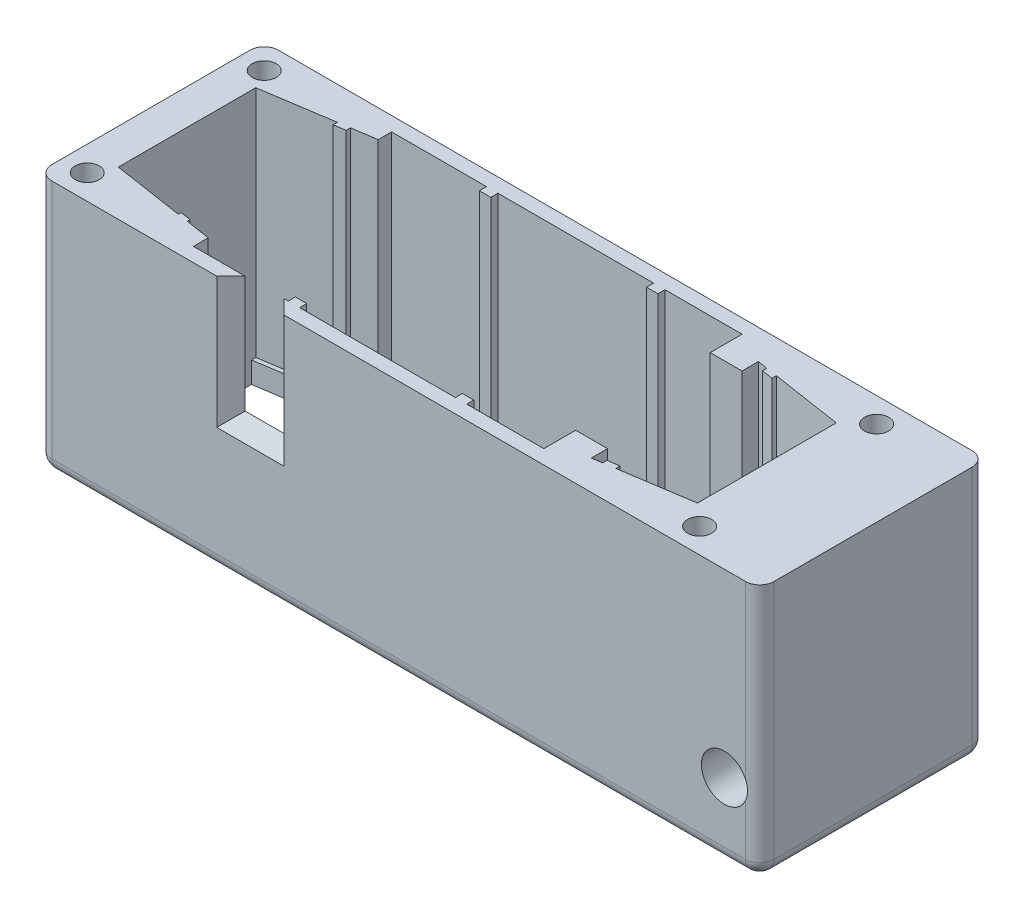
SolidWorks part; units mm, degrees
ref_plane "Front Plane" through (0, 0, 0) normal (0, 0, 1) x (1, 0, 0)
ref_plane "Top Plane" through (0, 0, 0) normal (0, 1, 0) x (1, 0, 0)
ref_plane "Right Plane" through (0, 0, 0) normal (1, 0, 0) x (0, 0, -1)
sketch "Sketch1" plane through (0, 0, 0) normal (0, 1, 0) x (1, 0, 0)
  line L0 (-28.64, -4.3272) -> (-28.64, -2.8272)
  line L1 (-28.64, 21.6728) -> (23.36, 21.6728)
  line L2 (-43.64, 17.8728) -> (-43.64, -0.5272)
  line L3 (-28.64, -4.3272) -> (23.36, -4.3272)
  line L4 (38.36, 17.8728) -> (38.36, -0.5272)
  line L5 (-28.64, -2.8272) -> (-43.64, -0.5272)
  line L6 (-43.64, 8.6728) -> (43.06, 8.6728) construction
  line L7 (-2.64, 26.6728) -> (-2.64, -4.3272) construction
  line L8 (23.36, -2.8272) -> (38.36, -0.5272)
  line L9 (23.36, -4.3272) -> (23.36, -2.8272)
  line L10 (-28.64, 21.6728) -> (-28.64, 20.1728)
  line L11 (-28.64, 20.1728) -> (-43.64, 17.8728)
  line L12 (23.36, 20.1728) -> (38.36, 17.8728)
  line L13 (23.36, 21.6728) -> (23.36, 20.1728)
  line L15 (-48.64, 24.6728) -> (53.36, 24.6728)
  line L16 (-48.64, 24.6728) -> (-48.64, -7.3272)
  line L17 (-48.64, -7.3272) -> (53.36, -7.3272)
  line L18 (53.36, 24.6728) -> (53.36, -7.3272)
  dimension "D1" = 82
  dimension "D2" = 15
  dimension "D3" = 1.5
  dimension "D4" = 9.2
  dimension "D5" = 15
  dimension "D6" = 5
  dimension "D7" = 3
  dimension "D8" = 3
  dimension "D9" = 26
extrude "main-body" add sketch "Sketch1" along normal blind 36
sketch "Sketch3" plane through (0, 36, 0) normal (0, 1, 0) x (1, 0, 0)
  line L0 (9.96, 22.6728) -> (23.36, 22.6728)
  line L1 (26.76, -2.3058) -> (28.36, -2.0605)
  line L2 (28.36, -2.6675) -> (38.36, -1.1342)
  line L3 (-2.64, 28.1728) -> (-2.64, -10.6272) construction
  line L6 (-33.64, 20.0132) -> (-33.64, 19.4062)
  line L7 (-28.64, 21.6728) -> (-28.6365, 20.7804)
  line L8 (-43.64, 18.4798) -> (-43.64, -0.9342)
  line L9 (-28.6365, -3.2347) -> (-32.14, -2.6975)
  line L10 (-13.64, -5.3272) -> (8.36, -5.3272)
  line L11 (-33.64, 20.0132) -> (-43.64, 18.4798)
  line L12 (-32.04, 19.6515) -> (-32.04, 20.2585)
  line L13 (-28.64, 20.1728) -> (-43.64, 17.8728) construction
  line L14 (-32.04, 19.6515) -> (-33.64, 19.4062)
  line L15 (-43.64, 17.8728) -> (-43.64, -0.5272) construction
  line L16 (-13.64, -5.3272) -> (-13.64, -4.3272)
  line L17 (23.36, 21.6728) -> (-28.64, 21.6728) construction
  line L18 (-28.64, 21.6728) -> (-28.64, 22.6728)
  line L19 (-28.64, 22.6728) -> (-15.24, 22.6728)
  line L20 (-15.24, -4.3272) -> (-13.64, -4.3272)
  line L21 (-15.24, -5.3272) -> (-15.24, -4.3272)
  line L22 (-15.24, 22.6728) -> (-15.24, 21.6728)
  line L23 (-15.24, 21.6728) -> (-13.64, 21.6728)
  line L24 (-13.64, 22.6728) -> (-13.64, 21.6728)
  line L25 (-13.64, 22.6728) -> (8.36, 22.6728)
  line L26 (-28.64, -5.3272) -> (-15.24, -5.3272)
  line L27 (-28.64, -4.1272) -> (-28.64, -5.3272)
  line L28 (-32.14, -2.0905) -> (-33.64, -1.8605)
  line L29 (-32.14, -2.0905) -> (-32.14, -2.6975)
  line L30 (-33.64, -2.4675) -> (-43.64, -0.9342)
  line L31 (-28.64, -4.1272) -> (-28.6365, -3.2347)
  line L32 (-33.64, -2.4675) -> (-33.64, -1.8605)
  line L33 (23.36, 22.6728) -> (23.36, 20.7798)
  line L34 (23.36, 20.1728) -> (23.36, 21.6728) construction
  line L35 (23.36, 20.7798) -> (26.76, 20.2585)
  line L36 (38.36, 17.8728) -> (23.36, 20.1728) construction
  line L37 (38.36, -0.5272) -> (38.36, 17.8728) construction
  line L38 (38.36, -1.1342) -> (38.36, 18.4798)
  line L39 (9.96, -5.3272) -> (23.36, -5.3272)
  line L40 (23.36, -5.3272) -> (23.36, -3.4342)
  line L41 (8.36, 22.6728) -> (8.36, 21.6728)
  line L42 (9.96, 21.6728) -> (8.36, 21.6728)
  line L43 (9.96, 22.6728) -> (9.96, 21.6728)
  line L44 (9.96, -5.3272) -> (9.96, -4.3272)
  line L45 (9.96, -4.3272) -> (8.36, -4.3272)
  line L46 (23.36, -4.3272) -> (23.36, -2.8272) construction
  line L47 (23.36, -3.4342) -> (26.76, -2.9129)
  line L48 (8.36, -5.3272) -> (8.36, -4.3272)
  line L49 (23.36, -2.8272) -> (38.36, -0.5272) construction
  line L50 (-28.64, -4.3272) -> (23.36, -4.3272) construction
  line L51 (28.36, 20.0132) -> (28.36, 19.4062)
  line L52 (26.76, -2.9129) -> (26.76, -2.3058)
  line L53 (26.76, 19.6515) -> (26.76, 20.2585)
  line L54 (28.36, 20.0132) -> (38.36, 18.4798)
  line L55 (26.76, 19.6515) -> (28.36, 19.4062)
  line L56 (-28.7309, 20.7659) -> (-43.7309, 18.4659)
  line L57 (-28.6365, 20.7804) -> (-32.04, 20.2585)
  line L58 (-43.64, 8.7728) -> (38.36, 8.7728) construction
  line L59 (28.36, -2.0605) -> (28.36, -2.6675)
  point P15 (-2.64, 30.1728)
  point P45 (-43.64, 8.7728)
  point P57 (-2.64, 22.6728)
  point P65 (-43.64, 8.7728)
  point P74 (-2.64, -5.3272)
  dimension "D1" = 1.6
  dimension "D2" = 10
  dimension "D3" = 1.6
  dimension "D4" = 1
  dimension "D5" = 11
  dimension "D7" = 0.6
  dimension "D8" = 0.6
  dimension "D9" = 1
  dimension "D10" = 10
  dimension "D11" = 1.6
  dimension "D12" = 41
  dimension "D6" = 0.6
extrude "clip-clearance" cut sketch "Sketch3" against normal offset from surface (33 mm away) 3 up to face at (2.36, 0, -8.6728)
sketch "Sketch4" plane through (0, 0, 0) normal (0, 1, 0) x (1, 0, 0)
  line L1 (23.36, 22.6728) -> (9.96, 22.6728) construction
  line L2 (20.8573, 22.6728) -> (25.3573, 22.6728)
  line L3 (20.8573, 22.6728) -> (20.8573, 18.1728)
  line L4 (20.8573, 18.1728) -> (25.3573, 18.1728)
  line L6 (-48.64, 8.6728) -> (53.36, 8.6728) construction
  line L8 (25.3573, 22.6728) -> (25.3573, 18.1728)
  line L9 (9.96, -5.3272) -> (23.36, -5.3272) construction
  line L10 (20.8573, -5.3272) -> (25.3573, -5.3272)
  line L11 (20.8573, -5.3272) -> (20.8573, -0.8272)
  line L17 (20.8573, -0.8272) -> (25.3573, -0.8272)
  line L18 (25.3573, -5.3272) -> (25.3573, -0.8272)
  line L19 (38.36, -1.1342) -> (38.36, 18.4798) construction
  line L20 (-48.64, 24.6728) -> (-48.64, -7.3272) construction
  line L21 (53.36, -7.3272) -> (53.36, 24.6728) construction
  dimension "D1" = 13.0028
  dimension "D2" = 13.0028
  dimension "D3" = 4.5
  dimension "D4" = 9.5
  dimension "D5" = 9.5
extrude "clip-guide" add sketch "Sketch4" along normal up to surface (36 mm away) up to face at (-2.6445, 36, -8.6917)
sketch "Sketch22" plane through (0, 0, 7.3272) normal (0, 0, 1) x (1, 0, 0)
  line L0 (-48.64, 36) -> (53.36, 36) construction
  line L1 (-16.34, 36) -> (-20.84, 36)
  line L2 (-16.34, 36) -> (-16.34, 20)
  line L3 (-16.34, 20) -> (-20.84, 20)
  line L4 (-20.84, 36) -> (-20.84, 20)
  line L5 (-48.64, 36) -> (-48.64, 0) construction
  line L7 (-48.64, 0) -> (53.36, 0) construction
  dimension "D1" = 27.8
  dimension "D2" = 4.5
  dimension "D3" = 20
extrude "clip-window" cut sketch "Sketch22" against normal up to next
sketch "Sketch5" plane through (53.36, 0, 0) normal (1, 0, 0) x (0, 0, -1)
  line L1 (2.6728, 22.82) -> (14.6728, 22.82)
  line L2 (2.6728, 22.82) -> (2.6728, 16.82)
  line L3 (2.6728, 16.82) -> (14.6728, 16.82)
  line L4 (14.6728, 22.82) -> (14.6728, 16.82)
  line L5 (-7.3272, 0) -> (24.6728, 0) construction
  line L6 (-7.3272, 36) -> (24.6728, 36) construction
  line L7 (8.6728, 36) -> (8.6728, 0) construction
  dimension "D1" = 22.82
  dimension "D2" = 6
  dimension "D3" = 12
  dimension "D4" = 6
extrude "lock_clearance" cut sketch "Sketch5" against normal offset from surface (18.5 mm away) 3.5 up to face at (38.36, 10.5, -8.6728) offset beyond the face yes
sketch "Sketch7" plane through (53.36, 0, 0) normal (1, 0, 0) x (0, 0, -1)
  line L0 (-7.3272, 0) -> (24.6728, 0) construction
  line L1 (2.6728, 16.82) -> (14.6728, 16.82)
  line L2 (2.6728, 16.82) -> (2.6728, 0)
  line L3 (2.6728, 0) -> (14.6728, 0)
  line L4 (14.6728, 16.82) -> (14.6728, 0)
  line L5 (14.6728, 16.82) -> (14.6728, 22.82) construction
extrude "lock_mech_clearance" cut sketch "Sketch7" against normal blind 10
sketch "Sketch26" plane through (0, 0, -14.6728) normal (0, 0, 1) x (1, 0, 0)
  line L0 (53.36, 22.82) -> (53.36, 0)
  line L1 (52.16, 2.5004) -> (50.86, 1.2004)
  line L2 (43.36, 0) -> (53.36, 0) construction
  line L3 (52.16, 2.5004) -> (52.16, 22.82)
  line L4 (38.36, 22.82) -> (53.36, 22.82) construction
  line L5 (53.36, 22.82) -> (52.16, 22.82)
  line L6 (53.36, 0) -> (50.86, 0)
  line L9 (50.86, 0) -> (50.86, 1.2004)
  dimension "D1" = 2.5
  dimension "D2" = 45
  dimension "D3" = 1.2
  dimension "D4" = 1.2004
extrude "lock_mech_cover" add sketch "Sketch26" along normal up to surface (12 mm away) up to face at (45.0267, 13.2133, -2.6728)
sketch "Sketch28" plane through (38.36, 0, 0) normal (-1, 0, 0) x (0, 0, 1)
  line L0 (-2.6728, 22.82) -> (-14.6728, 22.82) construction
  line L1 (-14.6728, 22.82) -> (-15.6728, 22.82)
  line L2 (-14.6728, 22.82) -> (-14.6728, 16.82)
  line L3 (-14.6728, 16.82) -> (-15.6728, 16.82)
  line L4 (-15.6728, 22.82) -> (-15.6728, 16.82)
  line L5 (-2.6728, 16.82) -> (-1.6728, 16.82)
  line L6 (-2.6728, 16.82) -> (-2.6728, 22.82)
  line L7 (-2.6728, 22.82) -> (-1.6728, 22.82)
  line L8 (-1.6728, 16.82) -> (-1.6728, 22.82)
  line L10 (-14.6728, 22.82) -> (-14.6728, 16.82) construction
  dimension "D1" = 1
  dimension "D2" = 1
extrude "lock_slide_clearance" cut sketch "Sketch28" against normal up to surface (13.8 mm away) up to face at (52.16, 12.6602, -8.6728)
sketch "Sketch27" plane through (0, 0, -14.6728) normal (0, 0, 1) x (1, 0, 0)
  line L0 (43.36, 0) -> (43.36, 4.5)
  line L1 (43.36, 0) -> (43.36, 16.82) construction
  line L2 (43.36, 4.5) -> (41.6257, 0)
  line L3 (53.36, 0) -> (-48.64, 0) construction
  line L4 (41.6257, 0) -> (43.36, 0)
  dimension "D1" = 4.5
  dimension "D2" = 1.7343
extrude "lock lever space" cut sketch "Sketch27" along normal up to surface (12 mm away) up to face at (48.7934, 6.2235, -2.6728)
hole_wizard "CBORE for M3 Hex Socket Thin Head Cap Screw2" positions "Sketch24" profile "Sketch23" counterbore size "M3" standard "DIN"
sketch "Sketch24" plane through (0, 0, 7.3272) normal (0, 0, 1) x (1, 0, 0)
  line L0 (53.36, 36) -> (53.36, 0) construction
  line L1 (-16.34, 36) -> (53.36, 36) construction
  point P0 (48.36, 10.5)
  dimension "D1" = 5
  dimension "D2" = 25.5
sketch "Sketch23" plane through (48.36, 10.5, 7.3272) normal (1, 0, 0) x (0, -1, 0)
  line L0 (0, 0) -> (0, 11.9614)
  line L1 (0, 11.9614) -> (1.6, 11)
  line L2 (1.6, 11) -> (1.6, 7.4)
  line L3 (1.6, 7.4) -> (3.25, 7.4)
  line L4 (3.25, 7.4) -> (3.25, 0)
  line L5 (3.25, 0) -> (0, 0)
  line L10 (0, 11.9614) -> (-1.6, 11) construction
  line L11 (0, -6.35) -> (0, 107.95) construction
  dimension "Hole Dia." = 3.2
  dimension "Hole Depth" = 11
  dimension "C'Bore Dia." = 6.5
  dimension "C'Bore Depth" = 7.4
  dimension "Drill Angle" = 118
hole_wizard "CBORE for M3 Hex Socket Thin Head Cap Screw1" positions "Sketch9" profile "Sketch8" counterbore size "M3" standard "DIN" end condition through all
sketch "Sketch9" plane through (0, 0, 0) normal (0, -1, 0) x (-1, 0, 0)
  line L0 (-53.36, -7.3272) -> (-53.36, 24.6728) construction
  line L1 (-53.36, 24.6728) -> (48.64, 24.6728) construction
  line L2 (48.64, -7.3272) -> (-53.36, -7.3272) construction
  line L3 (48.64, 24.6728) -> (48.64, -7.3272) construction
  point P0 (45.14, -3.8272)
  point P2 (-41.36, -3.8272)
  point P4 (-41.36, 21.1728)
  point P6 (45.14, 21.1728)
  dimension "D1" = 12
  dimension "D2" = 3.5
  dimension "D3" = 3.5
  dimension "D4" = 3.5
sketch "Sketch8" plane through (-45.14, 0, 3.8272) normal (1, 0, 0) x (0, 0, -1)
  line L0 (0, 0) -> (0, 36)
  line L1 (0, 36) -> (1.7, 36)
  line L2 (1.7, 18.225) -> (1.7, 36)
  line L3 (1.7, 18.225) -> (1.725, 18.2)
  line L4 (1.725, 18.2) -> (2.9, 18.2)
  line L5 (2.9, 18.2) -> (2.9, 0)
  line L7 (0, 0) -> (2.9, 0)
  line L9 (-1.7, 18.225) -> (-1.725, 18.2) construction
  line L11 (0, -6.35) -> (0, 107.95) construction
  dimension "Thru Hole Dia." = 3.4
  dimension "Thru Hole Depth" = 36
  dimension "C'Bore Dia." = 5.8
  dimension "C'Bore Depth" = 18.2
  dimension "Mid C'Sink Dia." = 3.45
  dimension "Mid C'Sink Angle" = 90
fillet "Fillet3" radius 2 2 edges at (2.36, 0, 7.3272) (2.36, 0, -24.6728)
chamfer "Chamfer1" distance 1 angle 45 4 edges at (25.3573, 0, 1.6741) (20.8573, 0, 2.5772) (25.3573, 0, -19.0197) (20.8573, 0, -19.9228)
chamfer "Chamfer2" distance 2.5 angle 45 3 edges at (-20.84, 28, 7.3272) (-18.59, 20, 7.3272) (-16.34, 28, 7.3272)
fillet "Fillet2" radius 2 10 edges at (-48.64, 19, -24.6728) (53.36, 19, -24.6728) (53.36, 19, 7.3272) (-48.64, 19, 7.3272) (53.36, 0, -8.6728) (-48.64, 0, -8.6728) (-48.64, 0.5858, -24.087) (53.36, 0.5858, -24.087) (53.36, 0.5858, 6.7414) (-48.64, 0.5858, 6.7414)
hole_wizard "M3 Tapped Hole1" positions "Sketch30" profile "Sketch29" tap size "M3" standard "DIN"
sketch "Sketch30" plane through (0, 0, -14.6728) normal (0, 0, 1) x (1, 0, 0)
  point P0 (48.36, 10.5)
sketch "Sketch29" plane through (48.36, 10.5, -14.6728) normal (1, 0, 0) x (0, -1, 0)
  line L0 (0, 0) -> (0, 8.7511)
  line L1 (0, 8.7511) -> (1.25, 8)
  line L2 (1.25, 8) -> (1.25, 0.5)
  line L3 (1.25, 0.5) -> (1.75, 0)
  line L5 (1.75, 0) -> (0, 0)
  line L6 (-1.25, 0.5) -> (-1.75, 0) construction
  line L10 (0, 8.7511) -> (-1.25, 8) construction
  line L11 (0, -6.35) -> (0, 107.95) construction
  dimension "Tap Drill Dia." = 2.5
  dimension "Tap Drill Depth" = 8
  dimension "Near C'Sink Dia." = 3.5
  dimension "Near C'Sink Angle" = 90
  dimension "Drill Angle" = 118
